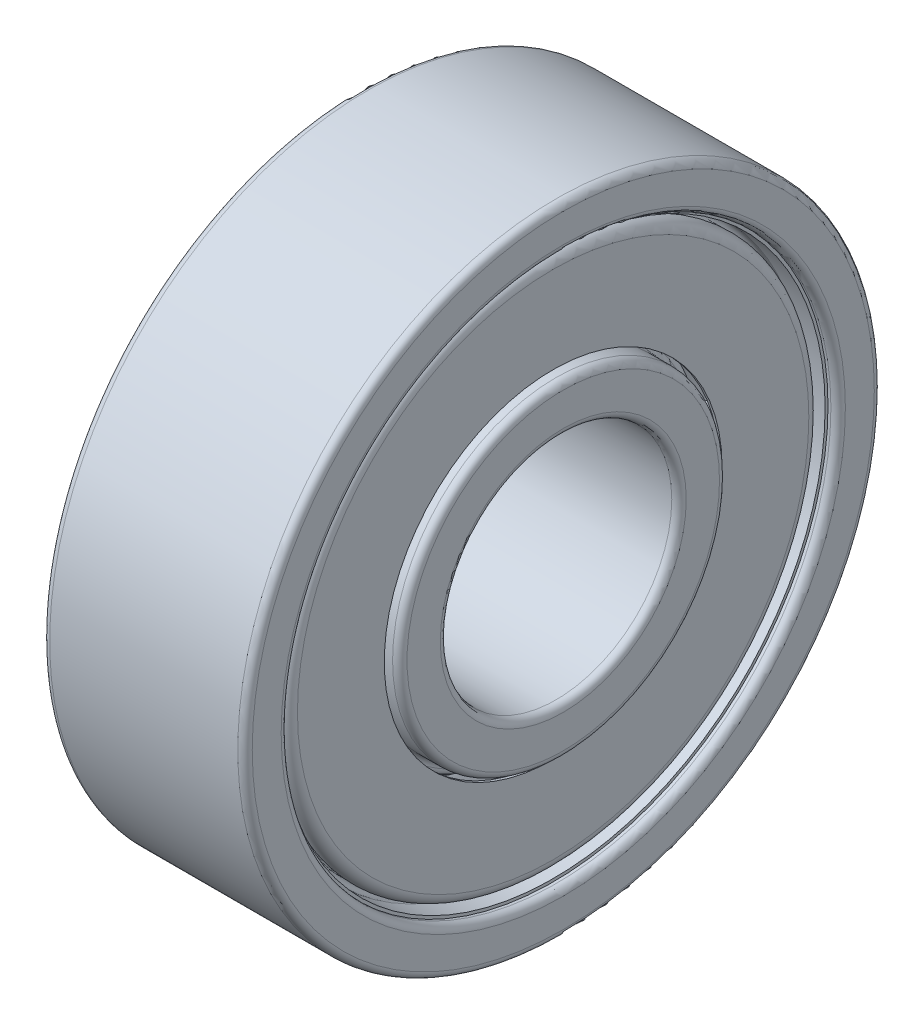
SolidWorks part; units mm, degrees
ref_plane "Front Plane" through (0, 0, 0) normal (0, 0, 1) x (1, 0, 0)
ref_plane "Top Plane" through (0, 0, 0) normal (0, 1, 0) x (1, 0, 0)
ref_plane "Right Plane" through (0, 0, 0) normal (1, 0, 0) x (0, 0, -1)
sketch "Sketch1" plane through (0, 0, 0) normal (1, 0, 0) x (0, 0, -1)
  circle A0 centre (0, 0) radius 11
  circle A1 centre (0, 0) radius 9
  dimension "D1" = 22
  dimension "D2" = 2
extrude "Boss-Extrude1" add sketch "Sketch1" along normal mid plane 7
sketch "Sketch3" plane through (0, 0, 0) normal (1, 0, 0) x (0, 0, -1)
  circle A0 centre (0, 0) radius 6.15
  circle A1 centre (0, 0) radius 4
  dimension "D1" = 12.3
  dimension "D2" = 8
extrude "Boss-Extrude2" add sketch "Sketch3" along normal mid plane 7 separate body
sketch "Sketch2" plane through (0, 0, 0) normal (0, 0, 1) x (1, 0, 0)
  line L0 (-3.5, 11) -> (-3.5, -11) construction
  line L1 (-2.2, 8.5) -> (-3.5, 8.5)
  line L2 (-2.2, 8.5) -> (-2.2, 9.5)
  line L3 (-2.2, 9.5) -> (-3.5, 9.5)
  line L4 (-3.5, 8.5) -> (-3.5, 9.5)
  line L6 (3.5, -9) -> (3.5, 9) construction
  line L7 (-3.5, 9) -> (-3.5, -9) construction
  line L8 (3.5, -11) -> (3.5, 11) construction
  line L9 (2.2, 8.5) -> (3.5, 8.5)
  line L10 (2.2, 8.5) -> (2.2, 9.5)
  line L11 (2.2, 9.5) -> (3.5, 9.5)
  line L12 (3.5, 8.5) -> (3.5, 9.5)
  line L13 (-3.5011, 5.65) -> (-2.1989, 5.65)
  line L14 (-3.5011, 5.65) -> (-3.5011, 6.65)
  line L16 (-3.5011, 6.65) -> (-2.1989, 6.65)
  line L17 (-2.1989, 5.65) -> (-2.1989, 6.65)
  line L20 (2.2, 5.65) -> (3.5, 5.65)
  line L21 (2.2, 5.65) -> (2.2, 6.65)
  line L22 (2.2, 6.65) -> (3.5, 6.65)
  line L23 (3.5, 5.65) -> (3.5, 6.65)
  circle A0 centre (0, 7.575) radius 2
  point P0 (-2.85, 9)
  point P9 (2.85, 9)
  point P22 (-2.85, 6.15)
  point P27 (2.85, 6.15)
  dimension "D5" = 4
  dimension "D6" = 1.925
  dimension "D1" = 1.3
  dimension "D2" = 1.3
  dimension "D3" = 0.5
ref_axis "Center Axis" through (3.5, 0, 0) along (-1, 0, 0)
revolve "Cut-Revolve1" cut sketch "Sketch2" angle 360 about axis through (3.5, 0, 0) along (-1, 0, 0)
sketch "Sketch9" plane through (0, 0, 0) normal (0, 0, 1) x (1, 0, 0)
  line L0 (0, 9.575) -> (0, 5.575)
  arc A0 (0, 9.575) -> (0, 5.575) centre (0, 7.575) ccw
revolve "Revolve1" add sketch "Sketch9" angle 360 about L0
pattern_circular "CirPattern2" count 7 over 360 about axis through (3.5, 0, 0) along (-1, 0, 0) of bodies 105
fillet "Fillet1" radius 0.25 10 edges at (1.4033, 0, 9) (-1.4033, 0, -9) (2.2, 0, 9) (2.2, 0, -9.5) (-2.2, 0, -9.5) (-2.2, 0, -9) (-3.5, 0, -9.5) (3.5, 0, -9.5) (-3.5, 0, -11) (3.5, 0, -11)
fillet "Fillet2" radius 0.25 9 edges at (-3.5, 0, -4) (1.4033, 0, 6.15) (-1.4033, 0, -6.15) (-2.1989, 0, -6.15) (-2.1989, 0, -5.65) (3.5, 0, -4) (2.2, 0, 6.15) (2.2, 0, -5.65) (3.5, 0, -5.65)
sketch "Sketch10" plane through (0, 0, 0) normal (0, 0, 1) x (1, 0, 0)
  line L0 (3.15, 9.5) -> (3.15, 9.4002)
  line L2 (2.4502, 9.4004) -> (3.15, 9.4002)
  line L4 (3.0504, 8.8342) -> (3.0504, 5.8372)
  line L5 (3.15, 8.8372) -> (3.15, 5.8372)
  line L6 (2.2, 9.5) -> (3.5, 9.5) construction
  line L8 (2.45, 9.5) -> (3.15, 9.5)
  line L9 (3.0504, 5.8372) -> (3.15, 5.8372)
  arc A0 (2.45, 9.5) -> (2.6035, 9.0527) centre (2.45, 9.25) ccw
  arc A1 (2.4502, 9.4004) -> (2.5424, 9.1313) centre (2.45, 9.25) ccw
  arc A2 (2.5424, 9.1313) -> (3.15, 8.8372) centre (2.7735, 8.8342) cw
  arc A3 (3.0504, 8.8342) -> (2.6035, 9.0527) centre (2.7735, 8.8342) ccw
  dimension "D6" = 3
revolve "Revolve2" add sketch "Sketch10" angle 360 about axis through (3.5, 0, 0) along (-1, 0, 0)
sketch "Sketch11" plane through (0, 0, 0) normal (0, 0, 1) x (1, 0, 0)
  line L2 (0, 6.575) -> (-2.2, 6.575)
  line L4 (0, 8.575) -> (-2.2, 8.575)
  line L6 (0.9104, 7.1612) -> (-2.2, 8.575) construction
  line L7 (0.9104, 7.9888) -> (-2.2, 6.575) construction
  line L8 (-2.2, 8.575) -> (-2.4057, 8.3693)
  line L9 (-2.2, 6.575) -> (-2.4057, 6.7807)
  line L10 (-2.4057, 6.7807) -> (-2.4057, 8.3693)
  arc A0 (0, 6.575) -> (0, 8.575) centre (0, 7.575) ccw
  point P0 (0, 7.575)
  point P1 (0, 7.575)
  point P2 (-2.2, 7.575)
revolve "Revolve3" add sketch "Sketch11" angle 360 about axis through (3.5, 0, 0) along (-1, 0, 0)
sketch "Sketch12" plane through (0, 0, 0) normal (0, 0, 1) x (1, 0, 0)
  line L0 (0, 9.625) -> (0, 5.525)
  arc A0 (0, 9.625) -> (0, 5.525) centre (0, 7.575) ccw
revolve "Cut-Revolve2" cut sketch "Sketch12" angle 360 about L0
pattern_circular "CirPattern3" count 7 over 360 about axis through (3.5, 0, 0) along (-1, 0, 0) of "Cut-Revolve2"
